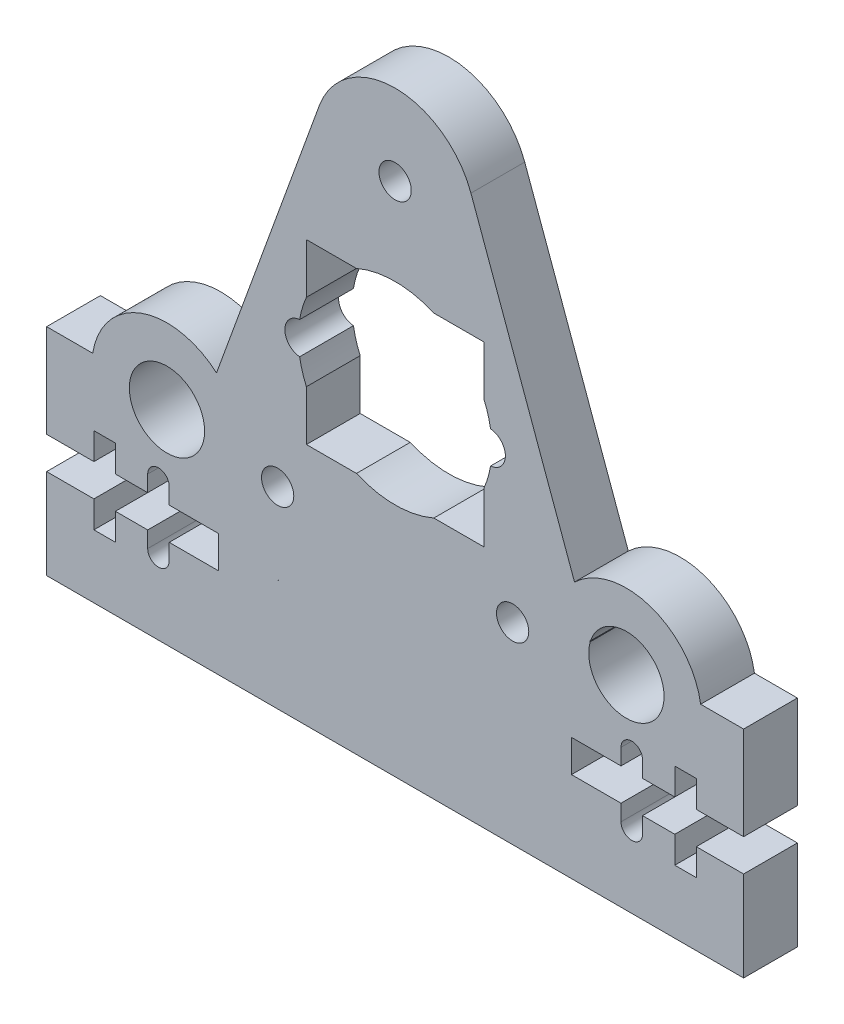
SolidWorks part; units mm, degrees
ref_plane "Front Plane" through (0, 0, 0) normal (0, 0, 1) x (1, 0, 0)
ref_plane "Top Plane" through (0, 0, 0) normal (0, 1, 0) x (1, 0, 0)
ref_plane "Right Plane" through (0, 0, 0) normal (1, 0, 0) x (0, 0, -1)
sketch "Sketch1" plane through (0, 0, 0) normal (0, 0, 1) x (1, 0, 0)
  line L0 (7.049, 19.6325) -> (17.9731, -10.4272)
  line L1 (-11.086, -20.4888) -> (10.9241, -20.4888)
  line L2 (-7.0493, 19.6315) -> (-17.9689, -10.4301)
  line L68 (-32.396, -10.8383) -> (-32.396, -30.8817)
  line L69 (-32.396, -10.8383) -> (32.396, -10.8383)
  line L70 (32.396, -10.8383) -> (32.396, -30.8817)
  line L71 (-32.396, -30.8817) -> (32.396, -30.8817)
  line L72 (-32.396, -10.8383) -> (32.396, -30.8817) construction
  line L73 (32.396, -10.8383) -> (-32.396, -30.8817) construction
  line L83 (8.2458, 8.2543) -> (3.5926, 8.2519)
  line L84 (-3.6012, 8.2481) -> (-8.2543, 8.2457)
  line L85 (-8.2543, 8.2457) -> (-8.2519, 3.5926)
  line L86 (-8.2481, -3.6012) -> (-8.2457, -8.2543)
  line L87 (-8.2457, -8.2543) -> (-3.5926, -8.2519)
  line L88 (3.6012, -8.2481) -> (8.2543, -8.2457)
  line L89 (8.2543, -8.2457) -> (8.2519, -3.5217)
  line L90 (8.2481, 3.672) -> (8.2458, 8.2543)
  arc A0 (7.049, 19.6325) -> (-7.0493, 19.6315) centre (0, 17.0709) ccw
  arc A1 (10.9241, -20.4888) -> (17.9731, -10.4272) centre (10.9241, -12.9888) ccw
  arc A2 (-17.9689, -10.4301) -> (-10.7531, -20.4888) centre (-10.9196, -12.9907) ccw
  circle A3 centre (0, 17.0709) radius 1.5
  circle A4 centre (10.9241, -12.9888) radius 1.5
  circle A5 centre (-10.9196, -12.9907) radius 1.5
  arc A6 (-28.1118, -10.8383) -> (-16.6025, -6.6683) centre (-21.209, -11.9221) cw
  arc A7 (16.6787, -6.8654) -> (28.4035, -10.8383) centre (21.5008, -11.9221) cw
  circle A8 centre (0, 0.0709) radius 17 construction
  circle A78 centre (21.5008, -11.9221) radius 3.5
  circle A79 centre (-21.209, -11.9221) radius 3.5
  arc A94 (3.5926, 8.2519) -> (-3.6012, 8.2481) centre (0, 0) ccw
  arc A95 (-8.2519, 3.5926) -> (-8.8758, 1.4902) centre (0, 0) ccw
  arc A96 (-8.8758, 1.4902) -> (-8.8742, -1.4994) centre (-8.75, -0.0045) ccw
  arc A97 (-8.8742, -1.4994) -> (-8.2481, -3.6012) centre (0, 0) ccw
  arc A98 (-3.5926, -8.2519) -> (3.6012, -8.2481) centre (0, 0) ccw
  arc A99 (8.2519, -3.5217) -> (8.8758, -1.4193) centre (0, 0.0709) ccw
  arc A100 (8.8758, -1.4193) -> (8.8742, 1.5702) centre (8.75, 0.0754) ccw
  arc A101 (8.8742, 1.5702) -> (8.2481, 3.672) centre (0, 0.0709) ccw
  point P18 (0, -20.86)
  dimension "D1" = 15
  dimension "D2" = 7
  dimension "D3" = 34
extrude "Boss-Extrude1" add sketch "Sketch1" along normal blind 5 contours A79 L69 A78 L0 A0 L2 A101 A100 A99 L89 L88 A98 L87 L86 A97 A96 A95 L85 L84 A94 L83 L90 A3 | A79 A2 L1 A1 A78 L69 A5 A4 | A79 L69 L68 L71 L70 A78 A1 L1 A2 | A79 L2 A6 L69 | A78 L69 A7 L0 region at (11.3885, 6.2108, 0) region at (22.5052, -7.7427, 0) region at (-0.0256, -23.2651, 0) region at (-22.3529, -7.7149, 0) region at (0.0494, -15.5713, 0)
sketch "Sketch2" plane through (0, 0, 5) normal (0, 0, 1) x (1, 0, 0)
  line L0 (26, -21.0069) -> (24.396, -21.0069) construction
  line L1 (26, -25) -> (28, -25)
  line L2 (26, -25) -> (26, -17.0138)
  line L3 (26, -17.0138) -> (28, -17.0138)
  line L4 (28, -25) -> (28, -17.0138)
  line L5 (32.396, -22.5069) -> (16.396, -22.5069)
  line L6 (32.396, -22.5069) -> (32.396, -19.5069)
  line L7 (32.396, -19.5069) -> (16.396, -19.5069)
  line L8 (16.396, -22.5069) -> (16.396, -19.5069)
  line L9 (32.396, -22.5069) -> (16.396, -19.5069) construction
  line L10 (32.396, -19.5069) -> (16.396, -22.5069) construction
  line L11 (22, -18.0069) -> (22, -24.0069) construction
  line L12 (23, -18.0069) -> (23, -24.0069)
  line L13 (21, -18.0069) -> (21, -24.0069)
  line L14 (32.396, -10.8383) -> (32.396, -30.8817) construction
  arc A0 (23, -18.0069) -> (21, -18.0069) centre (22, -18.0069) ccw
  arc A1 (21, -24.0069) -> (23, -24.0069) centre (22, -24.0069) ccw
  point P4 (24.396, -21.0069)
  point P17 (22, -21.0069)
  dimension "D1" = 3
  dimension "D2" = 16
  dimension "D3" = 2
  dimension "D4" = 8
  dimension "D5" = 3
extrude "Cut-Extrude3" cut sketch "Sketch2" against normal blind 10 contours L1 L4 L3 L2 | L5 L8 L7 L6 | A1 L12 A0 L13
mirror "Mirror1" about plane through (0, 0, 0) normal (1, 0, 0) of "Cut-Extrude3"
sketch "Sketch3" plane through (0, 0, 5) normal (0, 0, 1) x (1, 0, 0)
  line L0 (-7.0493, 19.6315) -> (-16.6025, -6.6683) construction
  line L1 (7.049, 19.6325) -> (16.6787, -6.8654) construction
  arc A0 (-9.7788, 12.1172) -> (9.7807, 12.1157) centre (0, 0) cw
  circle A1 centre (0, 17.0709) radius 1.5 construction
extrude "Cut-Extrude4" [suppressed] cut sketch "Sketch3" against normal through all and the other way through all
